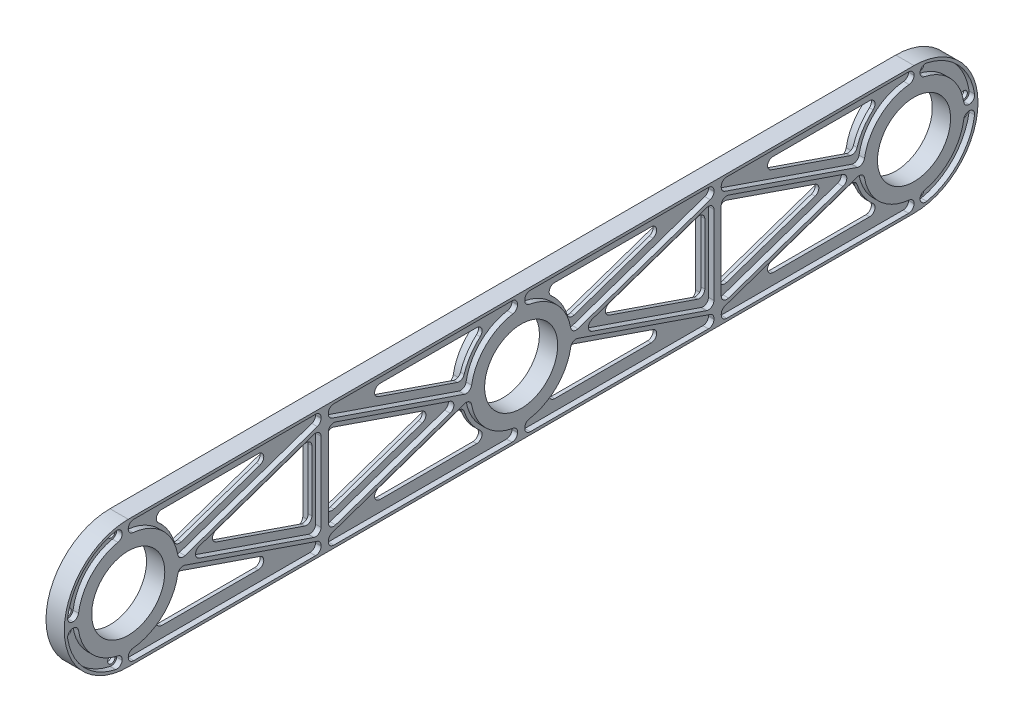
SolidWorks part; units mm, degrees
material "7050-T73510"
ref_plane "Front Plane" through (0, 0, 0) normal (0, 0, 1) x (1, 0, 0)
ref_plane "Top Plane" through (0, 0, 0) normal (0, 1, 0) x (1, 0, 0)
ref_plane "Right Plane" through (0, 0, 0) normal (1, 0, 0) x (0, 0, -1)
sketch "Sketch1" plane through (0, 0, 0) normal (1, 0, 0) x (0, 0, -1)
  line L0 (250, 0) -> (-250, 0) construction
  line L1 (250, 35) -> (-250, 35)
  line L2 (250, 35) -> (250, -35)
  line L3 (250, -35) -> (-250, -35)
  line L4 (-250, 35) -> (-250, -35)
  line L5 (250, 35) -> (-250, -35) construction
  line L6 (250, -35) -> (-250, 35) construction
  line L7 (0, 35) -> (0, -35) construction
  circle A0 centre (215, 0) radius 35
  circle A1 centre (-215, 0) radius 35
  point P0 (0, 0)
  dimension "D3" = 35
  dimension "D1" = 500
  dimension "D2" = 70
extrude "Boss-Extrude1" add sketch "Sketch1" along normal blind 10 contours L1 A1 L3 A0 | A0 | A1 region at (0, 0, 0) region at (0, 0, -215) region at (0, 0, 215)
sketch "Sketch2" plane through (0, 0, 0) normal (-1, 0, 0) x (0, 0, 1)
  line L0 (0, 35) -> (0, -35) construction
  line L3 (-215, 35) -> (215, 35) construction
  line L4 (-215, -35) -> (215, -35) construction
  circle A0 centre (0, 0) radius 20
  circle A1 centre (-215, 0) radius 20
  circle A2 centre (215, 0) radius 20
  dimension "D1" = 40
  dimension "D2" = 40
  dimension "D3" = 215
extrude "Cut-Extrude1" cut sketch "Sketch2" against normal blind 10
sketch "Sketch3" plane through (0, 0, 0) normal (-1, 0, 0) x (0, 0, 1)
  line L0 (-215, 27.5) -> (0, 27.5)
  line L1 (-187.5, 0) -> (-107.5, 27.5) construction
  line L2 (-215, -27.5) -> (0, -27.5)
  line L3 (-187.5, 0) -> (-107.5, -27.5) construction
  line L4 (-107.5, -27.5) -> (-27.5, 0) construction
  line L5 (-27.5, 0) -> (-107.5, 27.5) construction
  line L6 (-187.5, 0) -> (-27.5, 0)
  line L7 (-189.1254, 4.7284) -> (-107.5, 32.7872)
  line L8 (-25.8746, 4.7284) -> (-107.5, 32.7872)
  line L9 (-185.8746, 4.7284) -> (-107.5, -22.2128)
  line L10 (-107.5, -22.2128) -> (-29.1254, 4.7284)
  line L11 (-185.8746, -4.7284) -> (-107.5, 22.2128)
  line L12 (-29.1254, -4.7284) -> (-107.5, 22.2128)
  line L13 (-189.1254, -4.7284) -> (-107.5, -32.7872)
  line L14 (-107.5, -32.7872) -> (-25.8746, -4.7284)
  line L15 (-107.5, 27.5) -> (-107.5, -27.5) construction
  line L16 (-111.5, -20.8378) -> (-111.5, 20.8378)
  line L17 (-103.5, -20.8378) -> (-103.5, 20.8378)
  circle A0 centre (-215, 0) radius 27.5
  circle A1 centre (0, 0) radius 27.5
  dimension "D1" = 55
  dimension "D2" = 55
  dimension "D3" = 5
  dimension "D5" = 4
  dimension "D6" = 4
  dimension "D4" = 5
extrude "Cut-Extrude2" cut sketch "Sketch3" against normal blind 10 contours A0 L7 L0 | A0 L2 L13 | A1 L14 L2 | A1 L0 L8 | L17 L6 L12 | L17 L10 L6 | L9 L16 L6 | L6 L16 L11 region at (0, 20.3444, -171.0495) region at (0, -20.3444, -171.0495) region at (0, 20.3444, -43.9505) region at (0, -20.3444, -43.9505) region at (0, 6.9459, -131.7064) region at (0, -6.9459, -131.7064) region at (0, -6.9459, -83.2936) region at (0, 6.9459, -83.2936)
sketch "Sketch5" plane through (0, 0, 0) normal (-1, 0, 0) x (0, 0, 1)
  line L0 (-215, 27.5) -> (0, 27.5)
  line L1 (-215, -27.5) -> (0, -27.5)
  line L2 (0, 27.5) -> (0, 33.5)
  line L3 (0, 33.5) -> (-215, 33.5)
  line L4 (-215, 33.5) -> (-215, 27.5)
  line L6 (0, -27.5) -> (0, -33.5)
  line L7 (0, -33.5) -> (-215, -33.5)
  arc A0 (-215, 27.5) -> (-215, -27.5) centre (-215, 0) cw
  arc A1 (0, 27.5) -> (0, -27.5) centre (0, 0) ccw
  circle A2 centre (-215, 0) radius 33.5
  circle A3 centre (-215, 0) radius 27.5
  arc A4 (-187.9812, 5.1218) -> (-215, 27.5) centre (-215, 0) ccw construction
  line M2 (-187.9812, -5.1218) -> (-122.8808, -27.5)
  line M3 (-122.8808, -27.5) -> (-215, -27.5)
  line M5 (-27.0188, 5.1218) -> (-92.1192, 27.5)
  line M6 (-92.1192, 27.5) -> (0, 27.5)
  line M15 (-215, 27.5) -> (-122.8808, 27.5)
  line M16 (-122.8808, 27.5) -> (-187.9812, 5.1218)
  line M17 (-172.1192, 0) -> (-111.5, 20.8378)
  line M18 (-103.5, 20.8378) -> (-42.8808, 0)
  line M19 (-42.8808, 0) -> (-103.5, -20.8378)
  line M20 (-111.5, -20.8378) -> (-172.1192, 0)
  line M22 (0, -27.5) -> (-92.1192, -27.5)
  line M23 (-92.1192, -27.5) -> (-27.0188, -5.1218)
  line M39 (-111.5, 20.8378) -> (-111.5, -20.8378)
  line M41 (-103.5, -20.8378) -> (-103.5, 20.8378)
  dimension "D1" = 6
extrude "Cut-Extrude3" cut sketch "Sketch5" against normal blind 5 contours A2 L0 L2 L3 M6 | A2 L7 L6 L1 M22 M3 | A3 L4 A2 L1 | A2 L4 M15 | A2 L1 A1 L0 M2 M23 M5 M16 M19 M41 M18 M17 M39 M20 | A2 A0 M2 M16 region at (0, 30.5374, -101.0486) region at (0, 0, -105.7945) region at (0, 29.9194, -207.7316) region at (0, 0, -184.5469) region at (0, 0, -243.352) region at (0, -30.5374, -101.0486)
sketch "Sketch4" plane through (0, 0, 0) normal (-1, 0, 0) x (0, 0, 1)
  line L0 (-178.8626, 0) -> (-20, 0) construction
  line L1 (-171.3626, 0) -> (-107.5, -21.9528) construction
  line L2 (-107.5, -21.9528) -> (-43.6374, 0) construction
  line L3 (-43.6374, 0) -> (-107.5, 21.9528) construction
  line L4 (-107.5, 21.9528) -> (-171.3626, 0) construction
  line L5 (-107.5, -22.2128) -> (-107.5, 35) construction
  line L6 (-92.1192, 27.5) -> (-27.0188, 5.1218) construction
  line L7 (-122.8808, -27.5) -> (-187.9812, -5.1218) construction
  line L8 (-27.0188, -5.1218) -> (-92.1192, -27.5) construction
  line L9 (-122.8808, 27.5) -> (-187.9812, 5.1218) construction
  line L10 (-105.5, 27.8699) -> (-105.5, -27.8699)
  line L11 (-105.5, 27.8699) -> (-105.5, 33.5)
  line L12 (-105.5, 33.5) -> (-109.5, 33.5)
  line L13 (-109.5, 33.5) -> (-109.5, 27.8699)
  line L14 (-105.5, -27.8699) -> (-105.5, -33.5)
  line L15 (-24.4238, 0) -> (-107.5, 28.5574)
  line L16 (-107.5, 28.5574) -> (-190.5762, 0)
  line L17 (-190.5762, 0) -> (-107.5, -28.5574)
  line L18 (-107.5, -28.5574) -> (-24.4238, 0)
  line L19 (-30.5762, 0) -> (-107.5, 26.4426)
  line L20 (-109.5, -27.8699) -> (-109.5, 27.8699)
  line L21 (-107.5, 26.4426) -> (-184.4238, 0)
  line L22 (-184.4238, 0) -> (-107.5, -26.4426)
  line L23 (-107.5, -26.4426) -> (-30.5762, 0)
  line L24 (-105.5, -33.5) -> (-109.5, -33.5)
  line L25 (-109.5, -33.5) -> (-109.5, -27.8699)
  line L26 (-178.8626, 0) -> (-248, 0) construction
  line L27 (-215, -33.5) -> (-215, 33.5) construction
  line L28 (-215, 27.5) -> (-215, 33.5)
  line L29 (0, 33.5) -> (-215, 33.5) construction
  line L30 (-215, -33.5) -> (-215, -27.5)
  line L31 (-218.6491, -33.3007) -> (-217.9955, -27.3364)
  line L32 (-242.5, 0) -> (-248, 0) construction
  line L33 (-242.4591, 1.5) -> (-248.4664, 1.5)
  line L34 (-242.4591, -1.5) -> (-248.4664, -1.5)
  line L35 (-215, 33.5) -> (-215, 27.5)
  line L36 (-218.6491, 33.3007) -> (-217.9955, 27.3364)
  circle A1 centre (0, 0) radius 20 construction
  arc A2 (-215, 27.5) -> (-215, -27.5) centre (-215, 0) ccw
  arc A3 (-215, -33.5) -> (-215, 33.5) centre (-215, 0) cw
  arc M4 (0, 27.5) -> (0, -27.5) centre (0, 0) ccw
  line M48 (0, -33.5) -> (-215, -33.5)
  arc M49 (-215, -33.5) -> (-215, 33.5) centre (-215, 0) cw
  line M50 (-215, 33.5) -> (0, 33.5)
  dimension "D1" = 27.5
  dimension "D9" = 33.5
  dimension "D4" = 4
  dimension "D5" = 2
  dimension "D2" = 2
  dimension "D3" = 2
  dimension "D6" = 2
  dimension "D7" = 57.1149
  dimension "D8" = 51.9238
  dimension "D10" = 4.4238
  dimension "D11" = 57.4238
  dimension "D13" = 3
  dimension "D14" = 1.5
  dimension "D15" = 1.5
  dimension "D16" = 2
extrude "Boss-Extrude2" add sketch "Sketch4" against normal blind 6 contours L23 L10 L18 L15 L19 M4 | L16 L15 L11 L13 M50 | L21 L19 L10 L15 L16 L20 | L22 L21 L20 L16 L17 | L22 L23 L10 L19 L21 L20 | L23 L22 L20 L17 L18 L10 | L25 L14 L18 L17 M48 | A2 L28 L36 M49 | A2 L33 L34 M49 | A2 L31 L30 M49 region at (0, 13.5535, -66.8017) region at (0, 30.8531, -107.5) region at (0, 27.1562, -107.5) region at (0, 0, -107.5) region at (0, -27.1562, -107.5) region at (0, 26.8125, -110.4839) region at (0, -30.8531, -107.5) region at (0, 30.5376, -216.6682) region at (0, 0, -245.4876) region at (0, -30.5376, -216.6682)
sketch "Sketch6" plane through (10, 0, 0) normal (1, 0, 0) x (0, 0, -1)
  line L0 (0, 27.5) -> (215, 27.5)
  line L1 (215, -27.5) -> (0, -27.5)
  line L2 (0, 27.5) -> (0, 33.5)
  line L3 (0, 33.5) -> (215, 33.5)
  line L4 (215, 33.5) -> (215, 27.5)
  line L6 (0, -27.5) -> (0, -33.5)
  line L7 (0, -33.5) -> (215, -33.5)
  circle A0 centre (0, 0) radius 27.5
  circle A1 centre (215, 0) radius 27.5
  circle A2 centre (215, 0) radius 33.5
  line M1 (122.8808, -27.5) -> (187.9812, -5.1218)
  line M7 (92.1192, 27.5) -> (27.0188, 5.1218)
  line M24 (187.9812, 5.1218) -> (122.8808, 27.5)
  line M26 (103.5, -20.8378) -> (42.8808, 0)
  line M28 (42.8808, 0) -> (103.5, 20.8378)
  line M30 (111.5, 20.8378) -> (172.1192, 0)
  line M32 (172.1192, 0) -> (111.5, -20.8378)
  line M34 (27.0188, -5.1218) -> (92.1192, -27.5)
  arc M44 (187.9812, -5.1218) -> (215, -27.5) centre (215, 0) ccw
  line M45 (215, -27.5) -> (122.8808, -27.5)
  arc M46 (27.0188, 5.1218) -> (0, 27.5) centre (0, 0) ccw
  line M47 (0, 27.5) -> (92.1192, 27.5)
  line M48 (122.8808, 27.5) -> (215, 27.5)
  arc M49 (215, 27.5) -> (187.9812, 5.1218) centre (215, 0) ccw
  line M50 (92.1192, -27.5) -> (0, -27.5)
  arc M51 (0, -27.5) -> (27.0188, -5.1218) centre (0, 0) ccw
  dimension "D1" = 6
  dimension "D2" = 55
extrude "Cut-Extrude4" cut sketch "Sketch6" against normal blind 3 contours M7 M47 M46 | A1 L0 A0 L1 M24 M7 M34 M1 M26 M28 M30 M32 | M50 M34 M51 | M1 M45 M44 | M48 M24 M49 | A2 A1 M24 M1 | A2 L3 L2 L0 M47 M48 | L4 A2 L0 | A2 L4 A1 M45 | A2 L1 L6 L7 M50 region at (10, 30.5374, -101.0486) region at (10, 20.3444, -43.9505) region at (10, 0, -106.5299) region at (10, -20.3444, -43.9505) region at (10, -30.5374, -101.0486) region at (10, 23.0856, -238.0856) region at (10, 29.9194, -207.7316) region at (10, 18.2633, -192.3458) region at (10, 0, -184.5469) region at (10, -18.2633, -192.3458)
sketch "Sketch7" plane through (7, 0, -7) normal (-1, 0, 0) x (0, 0, 1)
  line L0 (-188, 0) -> (-13, 0) construction
  line L1 (-180.5, 0) -> (-100.5, -27.5) construction
  line L2 (-100.5, -27.5) -> (-20.5, 0) construction
  line L3 (-20.5, 0) -> (-100.5, 27.5) construction
  line L4 (-100.5, 27.5) -> (-180.5, 0) construction
  line L5 (-100.5, -22.2128) -> (-100.5, 35) construction
  line L6 (-98.5, 27.8699) -> (-98.5, 33.5)
  line L7 (7, 33.5) -> (-208, 33.5) construction
  line L8 (-98.5, 33.5) -> (-102.5, 33.5)
  line L9 (-102.5, 33.5) -> (-102.5, 27.8699)
  line L10 (-98.5, -27.8699) -> (-98.5, -33.5)
  line L11 (-17.4238, 0) -> (-100.5, 28.5574)
  line L12 (-100.5, 28.5574) -> (-183.5762, 0)
  line L13 (-183.5762, 0) -> (-100.5, -28.5574)
  line L14 (-100.5, -28.5574) -> (-17.4238, 0)
  line L15 (-23.5762, 0) -> (-100.5, 26.4426)
  line L16 (-100.5, 26.4426) -> (-177.4238, 0)
  line L17 (-177.4238, 0) -> (-100.5, -26.4426)
  line L18 (-100.5, -26.4426) -> (-23.5762, 0)
  line L19 (-98.5, -33.5) -> (-102.5, -33.5)
  line L20 (-102.5, -33.5) -> (-102.5, -27.8699)
  line L21 (-188, 0) -> (-241.5, 0) construction
  line L22 (-208, -33.5) -> (-208, 33.5) construction
  line L23 (-208, 27.5) -> (-208, 33.5)
  line L24 (-208, 33.5) -> (-207.8437, 33.028)
  line L25 (-208, -33.5) -> (-208, -27.5)
  line L26 (-211.6491, -33.3007) -> (-210.9955, -27.3364)
  line L27 (-235.5, 0) -> (-241.5, 0) construction
  line L28 (-235.0627, 1.5) -> (-241.5, 1.5)
  line L29 (-235.0627, -1.5) -> (-241.5, -1.5)
  line L30 (-208, 33.5) -> (-208, 27.5)
  line L31 (-211.6491, 33.3007) -> (-210.9955, 27.3364)
  line L32 (-235.5, -1.5) -> (-241.5, -1.5) construction
  line L33 (-235.5, 1.5) -> (-241.5, 1.5) construction
  line L34 (-98.5, -27.8699) -> (-98.5, 27.8699)
  line L35 (-102.5, 27.8699) -> (-102.5, -27.8699)
  circle A0 centre (7, 0) radius 20 construction
  arc A1 (-208, 33.5) -> (-208, -33.5) centre (-208, 0) ccw construction
  arc A2 (-208, 27.5) -> (-208, -27.5) centre (-208, 0) ccw
  arc A3 (-208, 27.5) -> (-208, -27.5) centre (-208, 0) ccw construction
  arc A4 (-208, -33.5) -> (-208, 33.5) centre (-208, 0) cw
  arc M74 (-208, 27.5) -> (-208, -27.5) centre (-208, 0) ccw
  arc M77 (-180.9812, -5.1218) -> (-180.9812, 5.1218) centre (-208, 0) ccw
  arc M81 (-20.0188, 5.1218) -> (-20.0188, -5.1218) centre (7, 0) ccw
  line M85 (7, -33.5) -> (-208, -33.5)
  arc M86 (-208, -33.5) -> (-208, 33.5) centre (-208, 0) cw
  line M87 (-208, 33.5) -> (7, 33.5)
  dimension "D7" = 3
  dimension "D1" = 87.5
  dimension "D4" = 87.5
  dimension "D5" = 2
  dimension "D6" = 2
  dimension "D8" = 1.5
  dimension "D9" = 1.5
  dimension "D2" = 1
  dimension "D3" = 1
extrude "Boss-Extrude3" add sketch "Sketch7" against normal blind 3 contours L14 L34 L18 L15 L11 M81 | L11 L12 L9 L6 M87 | L35 L16 L15 L34 L18 L17 | L35 L12 L11 L34 L15 L16 | L12 L35 L16 L17 L13 M77 | L35 L17 L18 L34 L14 L13 | L31 L23 M86 M74 | L29 L28 M74 M86 | L26 L25 M86 M74 | L20 L13 L14 L10 M85 region at (7, 30.8531, -107.5) region at (7, 27.1562, -107.5) region at (7, 13.5535, -66.8017) region at (7, 0, -107.5) region at (7, 26.8125, -110.4589) region at (7, -27.1563, -107.5) region at (7, 30.5376, -216.6682) region at (7, -30.8531, -107.5) region at (7, 0, -245.4876) region at (7, -30.5376, -216.6682)
sketch "Sketch8" plane through (10, 0, 0) normal (1, 0, 0) x (0, 0, -1)
  line L0 (0, 35) -> (0, -35) construction
  line L1 (215, 35) -> (-215, 35) construction
  line L2 (215, -35) -> (-215, -35) construction
sketch "Sketch9" plane through (0, 35, 0) normal (0, 1, 0) x (1, 0, 0)
  line L0 (10, 0) -> (0, 0) construction
  line L1 (10, 215) -> (10, -215) construction
  line L2 (0, 215) -> (0, -215) construction
ref_plane "Plane1" through (0, 0, 0) normal (0, 0, 1) x (1, 0, 0)
sketch "Sketch10" plane through (7, 0, 0) normal (1, 0, 0) x (0, 0, -1)
  circle A0 centre (0, 0) radius 27.5
  circle A1 centre (0, 0) radius 29.5
  circle A2 centre (215, 0) radius 27.5
  circle A3 centre (215, 0) radius 29.5
  arc A4 (27.4799, 1.0505) -> (0, 27.5) centre (0, 0) ccw construction
  circle A5 centre (215, 0) radius 27.5 construction
  line M3 (0, 33.5) -> (0, 27.5)
  line M4 (0, 27.5) -> (92.1192, 27.5)
  line M5 (92.1192, 27.5) -> (27.0188, 5.1218)
  line M7 (27.4799, 1.0505) -> (105.5, 27.8699)
  dimension "D1" = 2
  dimension "D2" = 2
extrude "Boss-Extrude4" add sketch "Sketch10" against normal blind 2 contours A3 A2 | A1 A0 M5 M4 | A1 A0 M3 M7 region at (7, 0.5413, -28.3292) region at (7, 27.1343, -5.3385) region at (7, 0, -186.3344)
sketch "Sketch11" plane through (10, 0, 0) normal (1, 0, 0) x (0, 0, -1)
  line L0 (0, 33.5) -> (0, 27.5)
  line L2 (0, 27.5) -> (2, 27.4272)
  line L3 (2, 27.4272) -> (2, 33.5)
  line L4 (2, 33.5) -> (0, 33.5)
  line L5 (27.8261, 0) -> (3.4851, 0) construction
  line L6 (2, -33.5) -> (0, -33.5)
  line L7 (2, -27.4272) -> (2, -33.5)
  line L8 (0, -27.5) -> (2, -27.4272)
  line L9 (0, -33.5) -> (0, -27.5)
  line L12 (0, 33.5) -> (105.5, 33.5) construction
  arc A0 (27.4799, 1.0505) -> (0, 27.5) centre (0, 0) ccw construction
  dimension "D1" = 2
extrude "Boss-Extrude5" add sketch "Sketch11" against normal blind 10
fillet "Fillet3" radius 3 86 edges at (6, 5.7782, -186.0714) (6, -5.7782, -28.9286) (2.5, 33.3007, -218.6491) (2.5, 27.3364, -217.9955) (2.5, 1.5, -248.4664) (2.5, 1.5, -242.4591) (2.5, -1.5, -242.4591) (2.5, -1.5, -248.4664) (2.5, -33.3007, -218.6491) (2.5, -27.3364, -217.9955) (6, -27.5, -204.3229) (2.5, -33.5, -215) (2.5, -27.5, -215) (2.5, -1.0505, -187.5201) (6, -5.7782, -186.0714) (6, 27.5, -122.8808) (2.5, 33.5, -109.5) (2.5, 27.8699, -109.5) (2.5, 33.5, -215) (2.5, 27.5, -215) (6, 27.5, -204.3229) (2.5, 1.0505, -187.5201) (6, 0, -172.1192) (2.5, 0, -184.4238) (6, -27.5, -122.8808) (2.5, -33.5, -109.5) (2.5, -27.8699, -109.5) (2.5, -27.8699, -105.5) (2.5, -33.5, -105.5) (6, -27.5, -92.1192) (6, -27.5, -10.6771) (2.5, -1.0505, -27.4799) (6, 0, -42.8808) (2.5, 0, -30.5762) (2.5, 1.0505, -27.4799) (2.5, 33.5, -105.5) (2.5, 27.8699, -105.5) (6, 27.5, -92.1192) (6, 5.7782, -28.9286) (6, 27.5, -10.6771) (8.5, 33.5, -105.5) (8.5, 27.8699, -105.5) (8.5, 1.0505, -27.4799) (8.5, -27.8699, -105.5) (8.5, -33.5, -105.5) (8.5, -1.0505, -27.4799) (8.5, 0, -30.5762) (8.5, 0, -184.4238) (8.5, -1.0505, -187.5201) (8.5, -27.8699, -109.5) (8.5, -33.5, -109.5) (8.5, -27.5, -215) (8.5, -33.5, -215) (8.5, -33.3007, -218.6491) (8.5, -27.3364, -217.9955) (8.5, 1.5, -242.4591) (8.5, 1.5, -248.4664) (8.5, 27.3364, -217.9955) (8.5, 33.3007, -218.6491) (8.5, 33.5, -215) (8.5, 27.5, -215) (8.5, 1.0505, -187.5201) (8.5, 33.5, -109.5) (8.5, 27.8699, -109.5) (2.5, 27.4272, -2) (2.5, 33.5, -2) (2.5, -27.4272, -2) (2.5, -33.5, -2) (8.5, -33.5, -2) (8.5, -27.4272, -2) (8.5, 33.5, -2) (8.5, 27.4272, -2) (8.5, 25.7551, -105.5) (8.5, 25.7551, -109.5) (8.5, -25.7551, -105.5) (8.5, -25.7551, -109.5) (6, -20.8378, -111.5) (2.5, -25.7551, -109.5) (6, -20.8378, -103.5) (2.5, -25.7551, -105.5) (6, 20.8378, -103.5) (2.5, 25.7551, -105.5) (2.5, 25.7551, -109.5) (6, 20.8378, -111.5) (8.5, -1.5, -242.4591) (8.5, -1.5, -248.4664)
hole_wizard "Ø4.0mm Dowel Hole1" positions "Sketch13" profile "Sketch12" hole size "Ø4.0" standard "ISO"
sketch "Sketch13" plane through (7, 0, 0) normal (1, 0, 0) x (0, 0, -1)
  arc A0 (221.9069, 32.7803) -> (218.3062, 30.1715) centre (221.2884, 29.8447) ccw construction
  arc A1 (245.1662, 1.5) -> (248.1334, 4.9426) centre (245.1662, 4.5) ccw construction
  arc A2 (248.1334, -4.9426) -> (245.1662, -1.5) centre (245.1662, -4.5) ccw construction
  arc A3 (218.3062, -30.1715) -> (221.9069, -32.7803) centre (221.2884, -29.8447) ccw construction
  point P0 (221.2884, 29.8447)
  point P2 (245.1662, 4.5)
  point P4 (245.1662, -4.5)
  point P6 (221.2884, -29.8447)
sketch "Sketch12" plane through (7, 29.8447, -221.2884) normal (0, 1, 0) x (0, 0, -1)
  line L0 (0, 0) -> (0, 18.4917)
  line L1 (0, 18.4917) -> (2, 17.29)
  line L2 (2, 17.29) -> (2, 0)
  line L5 (2, 0) -> (0, 0)
  line L10 (0, 18.4917) -> (-2, 17.29) construction
  line L11 (0, -6.35) -> (0, 107.95) construction
  dimension "Hole Dia." = 4
  dimension "Hole Depth" = 17.29
  dimension "Drill Angle" = 118
mirror "Mirror8" about plane through (0, 0, 0) normal (0, 0, 1) of "Ø4.0mm Dowel Hole1", "Boss-Extrude5", "Fillet3", "Cut-Extrude2", "Boss-Extrude4", "Cut-Extrude4", "Boss-Extrude3", "Cut-Extrude3", "Boss-Extrude2"
sketch "Sketch14" plane through (0, 0, 0) normal (-1, 0, 0) x (0, 0, 1)
  line L0 (-215, 35) -> (215, 35)
  line L1 (215, -35) -> (-215, -35)
  line L2 (-215, 33.5) -> (215, 33.5)
  line L3 (215, -33.5) -> (-215, -33.5)
  circle A0 centre (-215, 0) radius 35
  circle A1 centre (215, 0) radius 35
  circle A2 centre (-215, 0) radius 33.5
  circle A3 centre (215, 0) radius 33.5
  dimension "D1" = 1.5
  dimension "D2" = 1.5
extrude "Boss-Extrude6" [suppressed] add sketch "Sketch14" along normal blind 10 contours A2 L2 A0 L3 | A1 L0 A0 L2 | A1 L3 A0 L1 | A3 L3 A1 L2
